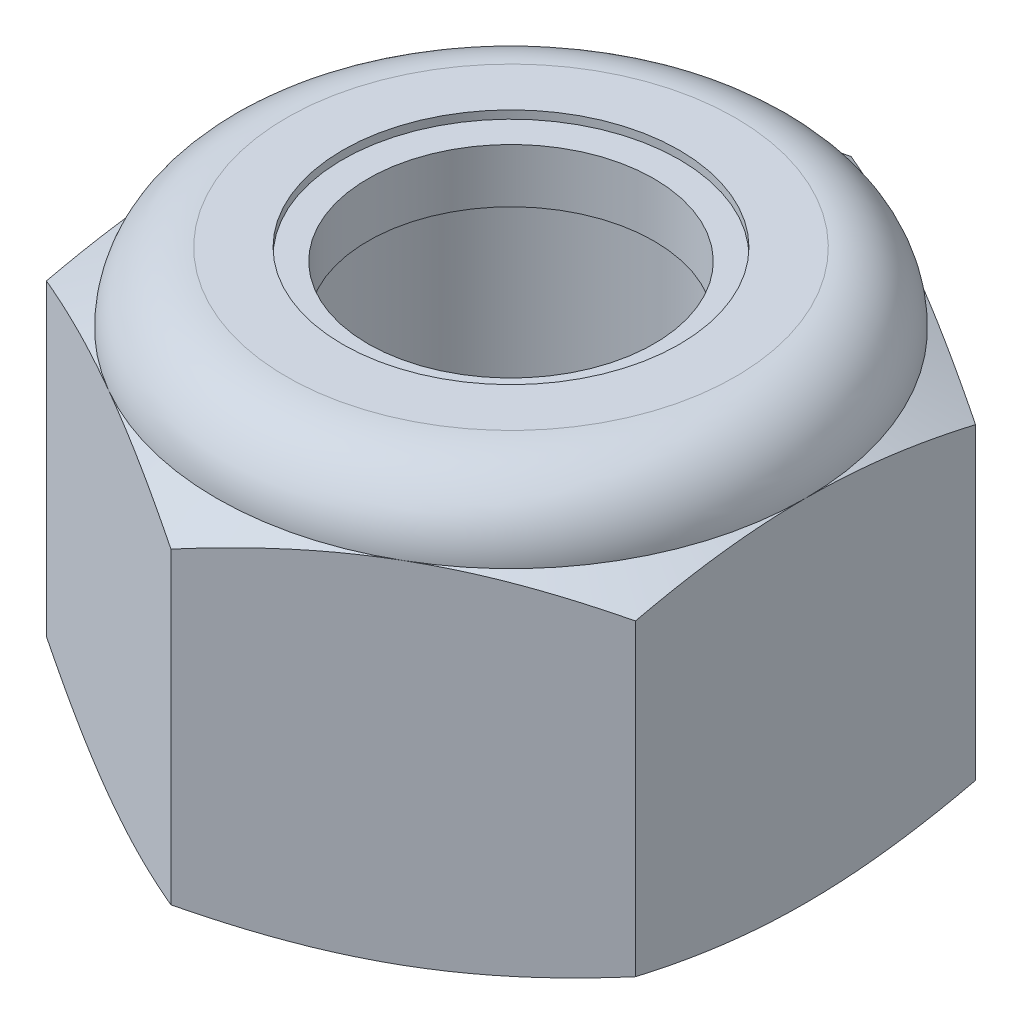
SolidWorks part; units mm, degrees
ref_plane "Front" through (0, 0, 0) normal (0, 0, 1) x (1, 0, 0)
ref_plane "Top" through (0, 0, 0) normal (0, 1, 0) x (1, 0, 0)
ref_plane "Right" through (0, 0, 0) normal (1, 0, 0) x (0, 0, -1)
sketch "Sketch1" plane through (0, 0, 0) normal (1, 0, 0) x (0, 0, -1)
  line L0 (0, 0) -> (0, 7.9375) construction
  line L1 (5.5562, 0) -> (-5.5562, 0) construction
  line L2 (-3.175, 7.9375) -> (3.175, 7.9375) construction
  line L3 (3.175, 7.9375) -> (3.175, 6.6675) construction
  point P9 (-3.175, 7.9375)
  point P10 (3.175, 7.9375)
  point P11 (5.5562, 0)
  dimension "Height" = 7.9375
  dimension "Hex Flats" = 11.1125
  dimension "Thread Dia" = 6.35
  dimension "Thread Pitch" = 1.27
sketch "Sketch13" plane through (0, 0, 0) normal (0, 1, 0) x (1, 0, 0)
  line L1 (0, 6.4158) -> (-5.5563, 3.2079)
  line L2 (-5.5563, 3.2079) -> (-5.5562, -3.2079)
  line L3 (-5.5562, -3.2079) -> (0, -6.4158)
  line L4 (0, -6.4158) -> (5.5563, -3.2079)
  line L5 (5.5563, -3.2079) -> (5.5563, 3.2079)
  line L6 (5.5563, 3.2079) -> (0, 6.4158)
  circle A0 centre (0, 0) radius 5.5562 construction
  circle A1 centre (0, 0) radius 3.175
  point P11 (0, -3.175)
  point P13 (0, 3.175)
extrude "Extrude1" add sketch "Sketch13" along normal up to vertex (7.9375 mm away) up to point (0, 7.9375, 0)
sketch "Sketch5" plane through (0, 0, 0) normal (1, 0, 0) x (0, 0, -1)
  line L0 (0, 0) -> (5.5562, 0)
  line L1 (5.5562, 0) -> (6.4158, 0.4008)
  line L2 (6.4158, 0.4008) -> (6.4158, 6.2138)
  line L3 (6.4158, 6.2138) -> (5.5562, 6.6146)
  line L4 (4.2333, 7.9375) -> (4.2333, 9.2075)
  line L5 (4.2333, 9.2075) -> (7.6858, 9.2075)
  line L6 (7.6858, 9.2075) -> (7.6858, -1.27)
  line L7 (7.6858, -1.27) -> (0, -1.27)
  line L8 (0, -1.27) -> (0, 0)
  line L9 (5.5562, 6.6146) -> (5.5562, 0) construction
  line L12 (6.4158, 7.9375) -> (6.4158, 0) construction
  line L13 (6.4158, 3.9688) -> (7.6858, 3.9688) construction
  line L15 (0, 0) -> (0, 9.2075) construction
  line L18 (5.5562, 0) -> (-5.5562, 0) construction
  line L19 (3.2079, 7.9375) -> (6.4158, 7.9375) construction
  line L20 (0, 9.2075) -> (4.2333, 9.2075) construction
  line L21 (3.2079, 0) -> (6.4158, 0) construction
  arc A0 (5.5562, 6.6146) -> (4.2333, 7.9375) centre (4.2333, 6.6146) ccw
  dimension "D1" = 25
  dimension "D2" = 1.27
  dimension "D4" = 1.3229
revolve "Cut-Revolve3" cut sketch "Sketch5" angle 360 about L15
sketch "Sketch4" plane through (0, 0, 0) normal (1, 0, 0) x (0, 0, -1)
  line L0 (0, 6.6146) -> (3.4925, 6.6146)
  line L1 (3.4925, 6.6146) -> (0, 4.986)
  line L3 (0, 1.6286) -> (3.4925, 0)
  line L4 (3.4925, 0) -> (0, 0)
  line L5 (0, 0) -> (0, 6.6146) construction
  line L10 (0, 0) -> (0, 7.9375) construction
  line L11 (0, 1.6286) -> (0, 0)
  line L12 (0, 6.6146) -> (0, 4.986)
  line L13 (4.8119, 6.6146) -> (0, 6.6146) construction
  dimension "D1" = 25
  dimension "D2" = 6.985
sketch "Sketch6" plane through (0, 0, 0) normal (1, 0, 0) x (0, 0, -1)
  line L0 (0, 6.6146) -> (5.4039, 6.6146)
  line L1 (4.2333, 7.7851) -> (2.1167, 7.7851)
  line L2 (0, 9.2075) -> (0, 6.6146)
  line L3 (2.1167, 9.2075) -> (0, 9.2075)
  line L4 (0, 9.2075) -> (4.2333, 9.2075) construction
  line L5 (0, 0) -> (0, 9.2075) construction
  line L6 (0, 9.2075) -> (0, 0) construction
  line L7 (2.1167, 7.7851) -> (2.1167, 9.2075)
  line L8 (4.2333, 7.9375) -> (4.2333, 7.7851) construction
  line L9 (2.1167, 7.7851) -> (0, 7.7851) construction
  line L10 (0, 7.7851) -> (0, 4.986) construction
  arc A0 (5.4039, 6.6146) -> (4.2333, 7.7851) centre (4.2333, 6.6146) ccw
  arc A1 (5.5562, 6.6146) -> (4.2333, 7.9375) centre (4.2333, 6.6146) ccw construction
  dimension "D1" = 0.1524
revolve "Cut-Revolve4" cut sketch "Sketch6" angle 360 about L6
revolve "Cut-Revolve2" cut sketch "Sketch4" angle 360 about L5
sketch "Sketch7" plane through (0, 0, 0) normal (1, 0, 0) x (0, 0, -1)
  line L0 (2.6988, 6.6908) -> (5.325, 6.6908)
  line L1 (4.2333, 7.7089) -> (2.6988, 7.7089)
  line L2 (2.6988, 7.7089) -> (2.6988, 6.6908)
  line L3 (2.6988, 6.6908) -> (0, 6.6908) construction
  line L4 (0, 6.6908) -> (0, 7.7089) construction
  line L5 (0, 7.7089) -> (2.6988, 7.7089) construction
  line L6 (2.6988, 6.6908) -> (2.6988, 6.6146) construction
  line L7 (0, 6.6146) -> (5.4039, 6.6146) construction
  line L8 (4.2333, 7.7089) -> (4.2333, 7.7851) construction
  arc A0 (5.325, 6.6908) -> (4.2333, 7.7089) centre (4.2333, 6.6146) ccw
  arc A2 (5.4039, 6.6146) -> (4.2333, 7.7851) centre (4.2333, 6.6146) ccw construction
  point P15 (2.6988, 7.7089)
  point P18 (-3.466, 7.7089)
  point P19 (3.466, 7.7089)
  dimension "D1" = 0.0762
  dimension "D2" = 5.3975
revolve "Revolve2" add sketch "Sketch7" angle 360 about L4
sketch "Sketch2" plane through (0, 0, 0) normal (1, 0, 0) x (0, 0, -1)
  line L0 (-3.175, 0) -> (-3.175, 6.6146) construction
  line L1 (0, 0) -> (3.175, 0)
  line L2 (0, 0) -> (0, 6.6146)
  line L3 (0, 6.6146) -> (3.175, 6.6146)
  line L4 (3.175, 0) -> (3.175, 6.6146)
  line L6 (4.8119, 6.6146) -> (5.5562, 6.6146) construction
  line L7 (0, -3.175) -> (0, 0) construction
revolve "Revolve1" [suppressed] add sketch "Sketch2" angle 360 about L7
sketch "Sketch9" [suppressed] plane through (0, 0, 0) normal (1, 0, 0) x (0, 0, -1)
  line L0 (3.3125, 7.8052) -> (3.3125, 6.5352) construction
  line L1 (3.3125, 6.5352) -> (2.2126, 7.1702) construction
  line L2 (2.2126, 7.1702) -> (3.3125, 7.8052) construction
  line L3 (2.3501, 7.2496) -> (2.3501, 7.0908) construction
  line L4 (3.175, 7.7258) -> (3.175, 6.6146) construction
  line L5 (2.2126, 7.1702) -> (2.3501, 7.1702) construction
  line L6 (3.175, 7.1702) -> (3.3125, 7.1702) construction
  line L7 (3.2437, 7.1702) -> (3.2437, 7.7655) construction
  line L8 (3.3125, 6.5352) -> (3.2437, 7.7655)
  line L9 (3.2437, 7.7655) -> (2.3501, 7.2496)
  line L10 (2.3501, 7.2496) -> (2.3501, 7.0908)
  line L11 (2.3501, 7.0908) -> (3.3125, 6.5352)
  dimension "D1" = 1.27
  dimension "D2" = 0.1588
sketch "Sketch10" [suppressed] plane through (0, 6.6146, 0) normal (0, 1, 0) x (1, 0, 0)
  circle A1 centre (0, 0) radius 3.175
  circle A2 centre (0, 0) radius 3.175
  dimension "D1" = 0
curve "Helix/Spiral1" [suppressed] pitch 1.27 height 9.2075 turns 7.25
sweep "Cut-Sweep1" [suppressed] cut profiles "Sketch9" path "Helix/Spiral1"
sketch "Sketch11" plane through (0, 0, 0) normal (1, 0, 0) x (0, 0, -1)
  line L0 (0, 0) -> (0, 7.9375) construction
  line L1 (5.5562, 0) -> (-5.5562, 0) construction
  line L4 (0, 7.9375) -> (0, 0) construction
  line L5 (0, 3.9688) -> (3.175, 3.9688) construction
  line L6 (0, 0) -> (3.4925, 0)
  line L7 (0, 1.6286) -> (0, 0)
  line L8 (3.4925, 0) -> (0, 1.6286)
  dimension "D1" = 6.985
  dimension "D2" = 25
revolve "Revolve3" [suppressed] add sketch "Sketch11" angle 360 about L4
sketch "Sketch12" plane through (0, 0, 0) normal (1, 0, 0) x (0, 0, -1)
  line L0 (3.4925, 6.6146) -> (0, 6.6146)
  line L1 (0, 6.6146) -> (0, 0)
  line L2 (0, 0) -> (3.4925, 0)
  line L3 (5.5562, 0) -> (-5.5562, 0) construction
  line L4 (3.4925, 0) -> (3.4925, 6.6146)
  line L5 (-3.4925, 0) -> (3.4925, 0) construction
revolve "Revolve4" [suppressed] add sketch "Sketch12" angle 360 about L0
combine bodies "Combine1" [suppressed] operation type subtract main body 136 bodies to subtract 133
equation "\"D4@Sketch5\" = \"Height@Sketch1\" / 6"
equation "\"D1@Sketch9\" = \"Thread Pitch@Sketch1\""
equation "\"D2@Sketch9\" = \"Thread Pitch@Sketch1\" / 8"
equation "\"D4@Helix/Spiral1\" = \"Thread Pitch@Sketch1\""
equation "\"D3@Helix/Spiral1\" = \"Thread Pitch@Sketch1\" + \"Height@Sketch1\""
equation "\"D2@Sketch4\" = \"Thread Dia@Sketch1\" * 1.1"
equation "\"D1@Sketch11\" = \"Thread Dia@Sketch1\" * 1.1"
equation "\"D2@Sketch7\" = \"Thread Dia@Sketch1\" * .85"
